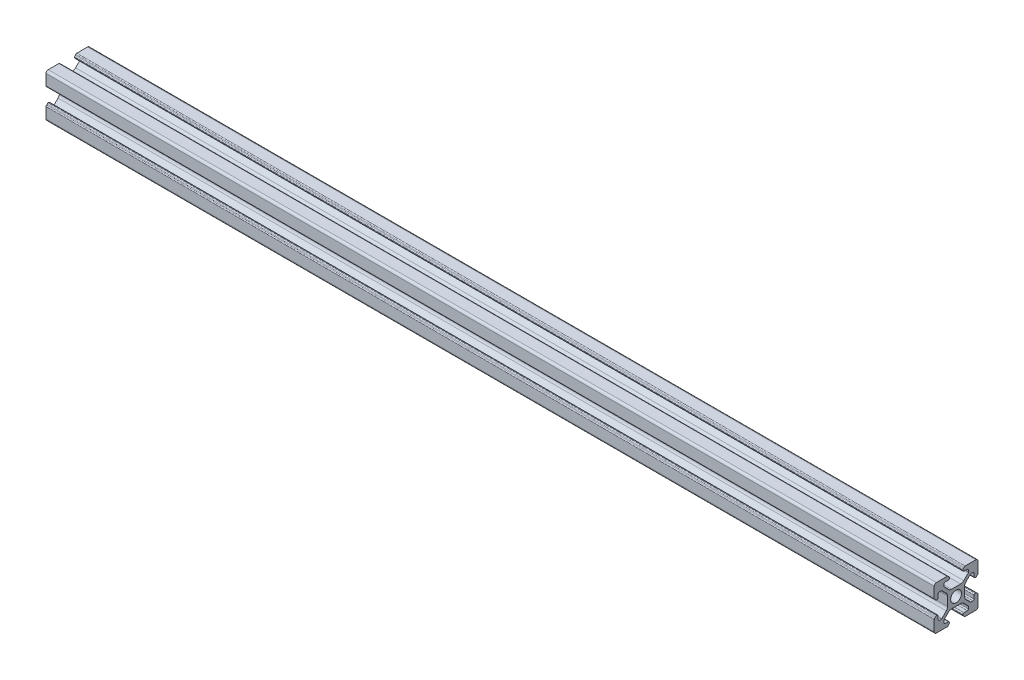
SolidWorks part; units mm, degrees
material "6063-O, Extruded Rod (SS)"
ref_plane "Front Plane" through (0, 0, 0) normal (0, 0, 1) x (1, 0, 0)
ref_plane "Top Plane" through (0, 0, 0) normal (0, 1, 0) x (1, 0, 0)
ref_plane "Right Plane" through (0, 0, 0) normal (1, 0, 0) x (0, 0, -1)
sketch "Sketch1" plane through (0, 0, 0) normal (1, 0, 0) x (0, 0, -1)
  line L0 (10, 10) -> (-10, -10) construction
  line L1 (-10, 10) -> (10, 10)
  line L2 (-10, 10) -> (-10, -10)
  line L3 (-10, -10) -> (10, -10)
  line L4 (10, 10) -> (10, -10)
  dimension "D1" = 20
extrude "Boss-Extrude1" add sketch "Sketch1" along normal blind 406
fillet "Fillet1" radius 1 4 edges at (203, -10, -10) (203, -10, 10) (203, 10, -10) (203, 10, 10)
sketch "Sketch3" plane through (0, 0, 0) normal (-1, 0, 0) x (0, 0, 1)
  line L0 (-3.6, 10) -> (3.6, 10)
  line L1 (-9, 10) -> (9, 10) construction
  line L2 (3.6, 10) -> (3.6, 9.5)
  line L3 (3.6, 9.5) -> (3.1, 9.5)
  line L4 (3.1, 9.5) -> (3.1, 8.2)
  line L5 (3.1, 8.2) -> (5.63, 8.2)
  line L6 (5.63, 8.2) -> (5.63, 6.6199)
  line L7 (5.63, 6.6199) -> (2.9101, 3.9)
  line L8 (2.9101, 3.9) -> (-2.9101, 3.9)
  line L9 (-2.9101, 3.9) -> (-5.63, 6.6199)
  line L10 (-5.63, 6.6199) -> (-5.63, 8.2)
  line L11 (-5.63, 8.2) -> (-3.1, 8.2)
  line L12 (-3.1, 8.2) -> (-3.1, 9.5)
  line L13 (-3.1, 9.5) -> (-3.6, 9.5)
  line L14 (-3.6, 9.5) -> (-3.6, 10)
  line L15 (0, 10) -> (0, 3.9) construction
  line L16 (10, 3.6) -> (10, -3.6)
  line L17 (10, -3.6) -> (9.5, -3.6)
  line L18 (9.5, -3.6) -> (9.5, -3.1)
  line L19 (9.5, -3.1) -> (8.2, -3.1)
  line L20 (8.2, -3.1) -> (8.2, -5.63)
  line L21 (8.2, -5.63) -> (6.6199, -5.63)
  line L22 (6.6199, -5.63) -> (3.9, -2.9101)
  line L23 (3.9, -2.9101) -> (3.9, 2.9101)
  line L24 (3.9, 2.9101) -> (6.6199, 5.63)
  line L25 (6.6199, 5.63) -> (8.2, 5.63)
  line L26 (8.2, 5.63) -> (8.2, 3.1)
  line L27 (8.2, 3.1) -> (9.5, 3.1)
  line L28 (9.5, 3.1) -> (9.5, 3.6)
  line L29 (9.5, 3.6) -> (10, 3.6)
  line L30 (10, 0) -> (3.9, 0) construction
  line L31 (3.6, -10) -> (-3.6, -10)
  line L32 (-3.6, -10) -> (-3.6, -9.5)
  line L33 (-3.6, -9.5) -> (-3.1, -9.5)
  line L34 (-3.1, -9.5) -> (-3.1, -8.2)
  line L35 (-3.1, -8.2) -> (-5.63, -8.2)
  line L36 (-5.63, -8.2) -> (-5.63, -6.6199)
  line L37 (-5.63, -6.6199) -> (-2.9101, -3.9)
  line L38 (-2.9101, -3.9) -> (2.9101, -3.9)
  line L39 (2.9101, -3.9) -> (5.63, -6.6199)
  line L40 (5.63, -6.6199) -> (5.63, -8.2)
  line L41 (5.63, -8.2) -> (3.1, -8.2)
  line L42 (3.1, -8.2) -> (3.1, -9.5)
  line L43 (3.1, -9.5) -> (3.6, -9.5)
  line L44 (3.6, -9.5) -> (3.6, -10)
  line L45 (0, -10) -> (0, -3.9) construction
  line L46 (-10, -3.6) -> (-10, 3.6)
  line L47 (-10, 3.6) -> (-9.5, 3.6)
  line L48 (-9.5, 3.6) -> (-9.5, 3.1)
  line L49 (-9.5, 3.1) -> (-8.2, 3.1)
  line L50 (-8.2, 3.1) -> (-8.2, 5.63)
  line L51 (-8.2, 5.63) -> (-6.6199, 5.63)
  line L52 (-6.6199, 5.63) -> (-3.9, 2.9101)
  line L53 (-3.9, 2.9101) -> (-3.9, -2.9101)
  line L54 (-3.9, -2.9101) -> (-6.6199, -5.63)
  line L55 (-6.6199, -5.63) -> (-8.2, -5.63)
  line L56 (-8.2, -5.63) -> (-8.2, -3.1)
  line L57 (-8.2, -3.1) -> (-9.5, -3.1)
  line L58 (-9.5, -3.1) -> (-9.5, -3.6)
  line L59 (-9.5, -3.6) -> (-10, -3.6)
  line L60 (-10, 0) -> (-3.9, 0) construction
  line L61 (10, 9) -> (10, -9) construction
  line L62 (-10, -9) -> (-10, 9) construction
  point P4 (0, 10)
  point P17 (0, 0)
  point P26 (10, 0)
  point P43 (0, -10)
  point P60 (-10, 0)
  point P75 (0, 0)
  dimension "D1" = 135
  dimension "D2" = 6.2
  dimension "D3" = 7.2
  dimension "D4" = 6.1
  dimension "D5" = 11.26
  dimension "D6" = 0.5
  dimension "D8" = 1.4
  dimension "D9" = 1.8
  dimension "D7" = 4
extrude "Cut-Extrude1" cut sketch "Sketch3" against normal through all
hole_wizard "Ø5.0 (5) Diameter Hole1" positions "Sketch4" profile "Sketch5" hole size "Ø5.0" standard "ANSI Metric" end condition through all
sketch "Sketch4" plane through (0, 0, 0) normal (-1, 0, 0) x (0, 0, 1)
  point P0 (0, 0)
sketch "Sketch5" plane through (0, 0, 0) normal (0, 1, 0) x (0, 0, 1)
  line L0 (0, 0) -> (0, 406)
  line L1 (0, 406) -> (2.5, 406)
  line L2 (2.5, 406) -> (2.5, 0)
  line L5 (2.5, 0) -> (0, 0)
  line L11 (0, -6.35) -> (0, 107.95) construction
  dimension "Thru Hole Dia." = 5
  dimension "Thru Hole Depth" = 406
fillet "Fillet2" radius 2 8 edges at (203, -3.9, -2.9101) (203, -3.9, 2.9101) (203, -2.9101, 3.9) (203, 2.9101, 3.9) (203, 3.9, 2.9101) (203, 3.9, -2.9101) (203, 2.9101, -3.9) (203, -2.9101, -3.9)
fillet "Fillet3" radius 0.5 20 edges at (203, 3.6, -10) (203, 3.1, -9.5) (203, 3.1, -8.2) (203, 5.63, -8.2) (203, 5.63, -6.6199) (203, 3.6, 10) (203, 3.1, 9.5) (203, 3.1, 8.2) (203, 5.63, 8.2) (203, 5.63, 6.6199) (203, 6.6199, 5.63) (203, 8.2, 5.63) (203, 8.2, 3.1) (203, 9.5, 3.1) (203, 10, 3.6) (203, 9.5, -3.1) (203, 10, -3.6) (203, 8.2, -3.1) (203, 8.2, -5.63) (203, 6.6199, -5.63)
fillet "Fillet4" radius 0.5 20 edges at (203, -3.6, 10) (203, -3.1, 9.5) (203, -3.1, 8.2) (203, -5.63, 8.2) (203, -5.63, 6.6199) (203, -6.6199, 5.63) (203, -8.2, 5.63) (203, -8.2, 3.1) (203, -10, 3.6) (203, -9.5, 3.1) (203, -10, -3.6) (203, -9.5, -3.1) (203, -8.2, -3.1) (203, -8.2, -5.63) (203, -6.6199, -5.63) (203, -5.63, -6.6199) (203, -5.63, -8.2) (203, -3.1, -8.2) (203, -3.1, -9.5) (203, -3.6, -10)
fillet "Fillet5" radius 0.5 8 edges at (203, 3.6, -9.5) (203, -3.6, -9.5) (203, -9.5, -3.6) (203, -9.5, 3.6) (203, -3.6, 9.5) (203, 3.6, 9.5) (203, 9.5, 3.6) (203, 9.5, -3.6)
